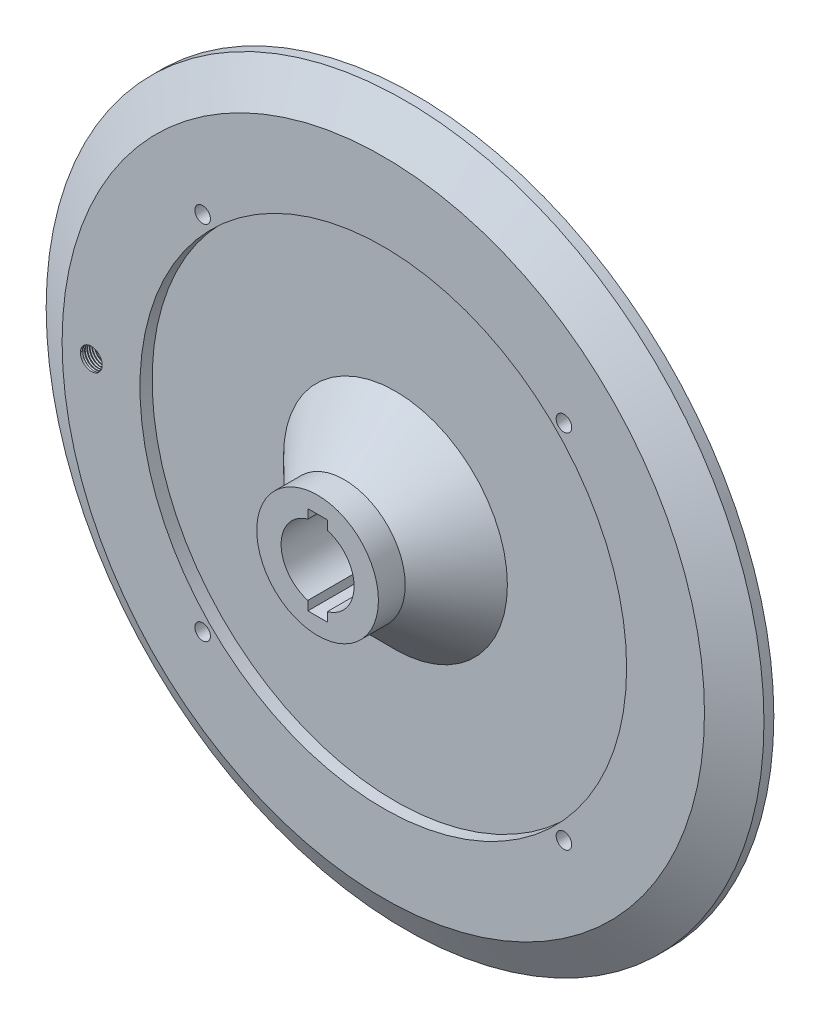
SolidWorks part; units mm, degrees
ref_plane "Piano frontale" through (0, 0, 0) normal (0, 0, 1) x (1, 0, 0)
ref_plane "Piano superiore" through (0, 0, 0) normal (0, 1, 0) x (1, 0, 0)
ref_plane "Piano destro" through (0, 0, 0) normal (1, 0, 0) x (0, 0, -1)
sketch "Schizzo1" plane through (0, 0, 0) normal (0, 0, 1) x (1, 0, 0)
  circle A0 centre (0, 0) radius 147.5
  circle A1 centre (0, 0) radius 15
  dimension "D1" = 30
  dimension "D2" = 295
extrude "Estrusione-Estrusione1" add sketch "Schizzo1" along normal blind 52
sketch "Schizzo2" plane through (0, 0, 52) normal (0, 0, 1) x (1, 0, 0)
  circle A0 centre (0, 0) radius 147.5 construction
  circle A1 centre (0, 0) radius 147.5
  circle A2 centre (0, 0) radius 25
  dimension "D1" = 50
extrude "Taglio-Estrusione2" cut sketch "Schizzo2" against normal blind 27
sketch "Schizzo3" plane through (0, 0, 25) normal (0, 0, 1) x (1, 0, 0)
  circle A0 centre (0, 0) radius 100
  circle A1 centre (0, 0) radius 25 construction
  circle A2 centre (0, 0) radius 25
  dimension "D1" = 200
extrude "Taglio-Estrusione3" cut sketch "Schizzo3" against normal blind 5
chamfer "Smusso1" distance 21 angle 45 1 edges at (25, 0, 20)
chamfer "Smusso2" distance 15.5 angle 30 1 edges at (147.5, 0, 25) first distance on face at (100, 0, 25)
sketch "Schizzo7" plane through (0, 0, 25) normal (0, 0, 1) x (1, 0, 0)
  circle A0 centre (0, 0) radius 120 construction
  point P3 (-120, 0)
  dimension "D1" = 240
hole_wizard "Foro per Vite M8-1" positions "Schizzo3D3" profile "Schizzo8" hole size "M8" standard "Ansi Metric" end condition through all
sketch3d "Schizzo3D3"
  point P0 (-120, 0, 25)
sketch "Schizzo8" plane through (-120, 0, 25) normal (1, 0, 0) x (0, -1, 0)
  line L0 (0, 0) -> (0, 25)
  line L1 (0, 25) -> (4.5, 25)
  line L2 (4.5, 25) -> (4.5, 0)
  line L5 (4.5, 0) -> (0, 0)
  line L11 (0, -6.35) -> (0, 107.95) construction
  dimension "Thru Hole Dia." = 9
  dimension "Thru Hole Depth" = 25
thread "Filettatura1" pitch 1 method cut profile "Profilo filettatura1" start angle 0, offset 0, length 10, pitch 1, diameter 9
ref_plane "Piano1" through (-124.5, 0, 25) normal (0, -1, 0) x (-1, 0, 0)
sketch "Profilo filettatura1" plane through (-124.5, 0, 25) normal (0, -1, 0) x (-1, 0, 0)
  line L0 (0, 0) -> (0, 1) construction
  line L1 (0, 0) -> (0.5413, 0.3125)
  line L2 (0.5413, 0.3125) -> (0.5413, 0.4375)
  line L3 (0.5413, 0.4375) -> (0, 0.75)
  line L4 (0.5413, 0.375) -> (0, 0.375) construction
  line L11 (0, 0) -> (0, 0.75)
  point P2 (0, 0)
  dimension "Pitch" = 1
  dimension "Profile_Angle" = 60
  dimension "Profile_Land" = 0.125
  dimension "Profile_Height" = 0.5413
sketch "Schizzo21" plane through (0, 0, 0) normal (0, 0, -1) x (-1, 0, 0)
  circle A0 centre (0, 0) radius 95
  dimension "D1" = 190
extrude "Taglio-Estrusione5" cut sketch "Schizzo21" against normal blind 5
chamfer "Smusso3" distance 5 angle 45 1 edges at (-95, 0, 5)
sketch "Schizzo22" plane through (0, 0, 52) normal (0, 0, 1) x (1, 0, 0)
  line L1 (-4, -18.2) -> (4, -18.2)
  line L2 (-4, -18.2) -> (-4, 18.2)
  line L3 (-4, 18.2) -> (4, 18.2)
  line L4 (4, -18.2) -> (4, 18.2)
  line L5 (-4, -18.2) -> (4, 18.2) construction
  line L6 (-4, 18.2) -> (4, -18.2) construction
  point P0 (0, 0)
  dimension "D1" = 8
  dimension "D2" = 36.4
extrude "Taglio-Estrusione6" cut sketch "Schizzo22" against normal through all
sketch "Schizzo23" plane through (0, 0, 0) normal (0, 1, 0) x (1, 0, 0)
  line L1 (147.5, 0) -> (90, 0)
  line L2 (147.5, 0) -> (147.5, -12)
  line L3 (147.5, -12) -> (90, -12)
  line L4 (90, 0) -> (90, -12)
  line L5 (0, -16.0511) -> (0, 0) construction
  dimension "D1" = 90
  dimension "D2" = 12
revolve "Taglia-Rivoluzione1" cut sketch "Schizzo23" angle 360 about axis through (0, 0, 52) along (0, 0, -1)
hole_wizard "Foro per Vite M6-2" positions "Schizzo24" profile "Schizzo26" hole size "M6" standard "ISO" end condition through all
sketch "Schizzo24" plane through (0, 0, 0) normal (0, 0, 1) x (1, 0, 0)
  line L0 (0, 0) -> (-74.2462, 74.2462) construction
  point P0 (-74.2462, 74.2462)
  dimension "D1" = 105
sketch "Schizzo26" plane through (-74.2462, 74.2462, 0) normal (1, 0, 0) x (0, 1, 0)
  line L0 (0, 0) -> (0, 52)
  line L1 (0, 52) -> (3.2, 52)
  line L2 (3.2, 52) -> (3.2, 0)
  line L5 (3.2, 0) -> (0, 0)
  line L11 (0, -6.35) -> (0, 107.95) construction
  dimension "Thru Hole Dia." = 6.4
  dimension "Thru Hole Depth" = 52
pattern_circular "RipetizioneCircolare1" count 4 over 360 about axis through (0, 0, 52) along (0, 0, 1) of "Foro per Vite M6-2"
sketch "Schizzo29" plane through (0, 0, 12) normal (0, 0, -1) x (-1, 0, 0)
  circle A0 centre (120, 0) radius 6.25
  circle A2 centre (120, 0) radius 8.1
  dimension "D1" = 16.2
  dimension "D2" = 12.5
extrude "Taglio-Estrusione7" cut sketch "Schizzo29" against normal blind 1.8
